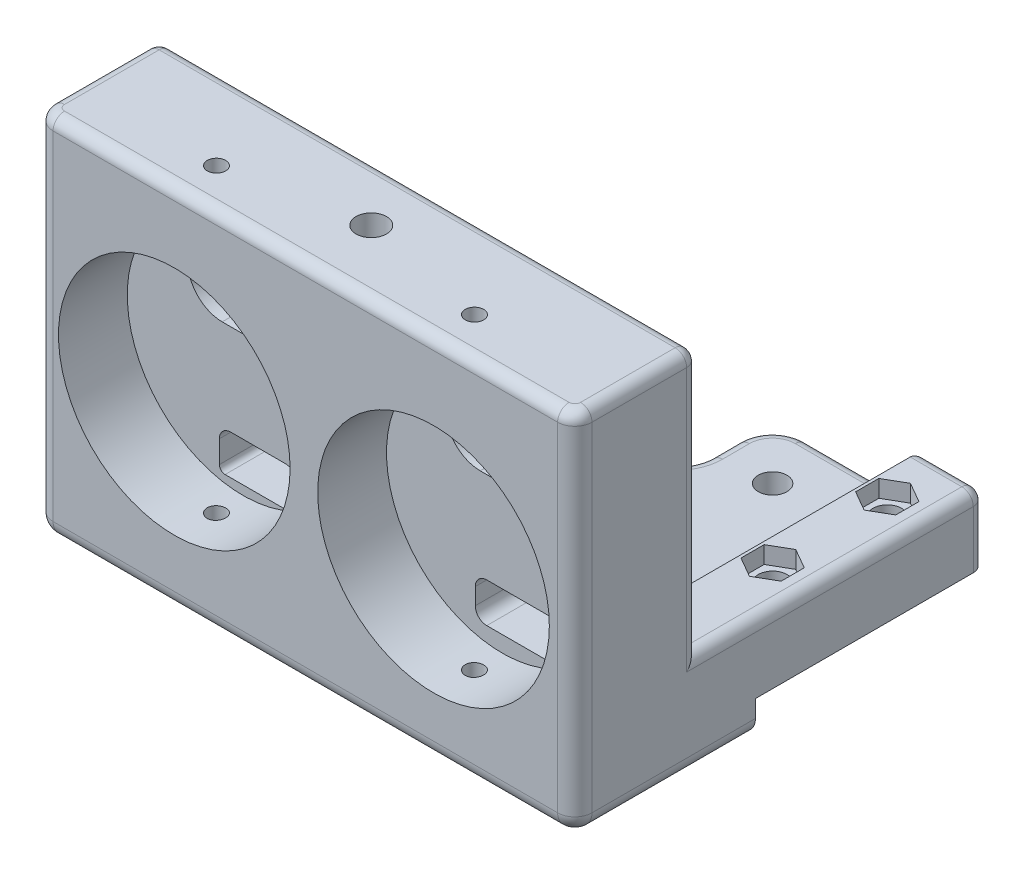
SolidWorks part; units mm, degrees
ref_plane "Ebene vorne" through (0, 0, 0) normal (0, 0, 1) x (1, 0, 0)
ref_plane "Ebene oben" through (0, 0, 0) normal (0, 1, 0) x (1, 0, 0)
ref_plane "Ebene rechts" through (0, 0, 0) normal (1, 0, 0) x (0, 0, -1)
sketch "Skizze1" plane through (0, 0, 0) normal (0, 0, 1) x (1, 0, 0)
  line L1 (174.4691, 28.0437) -> (80.4691, 28.0437)
  line L2 (174.4691, 28.0437) -> (174.4691, -35.9563)
  line L3 (174.4691, -35.9563) -> (80.4691, -35.9563)
  line L4 (80.4691, 28.0437) -> (80.4691, -35.9563)
extrude "Aufsatz-Linear austragen1" add sketch "Skizze1" along normal blind 21.5
sketch "Skizze2" plane through (0, 0, 0) normal (0, 0, -1) x (-1, 0, 0)
  line L5 (-174.4691, -35.9563) -> (-174.4691, 28.0437) construction
  line L6 (-174.4691, -17.9563) -> (-80.4691, -17.9563)
  line L7 (-174.4691, -17.9563) -> (-174.4691, -29.9563)
  line L8 (-174.4691, -29.9563) -> (-80.4691, -29.9563)
  line L9 (-80.4691, -17.9563) -> (-80.4691, -29.9563)
  line L10 (-80.4691, 28.0437) -> (-80.4691, -35.9563) construction
  line L16 (-80.4691, -35.9563) -> (-174.4691, -35.9563) construction
  dimension "D1" = 94
  dimension "D2" = 6
  dimension "D3" = 12
extrude "Aufsatz-Linear austragen2" add sketch "Skizze2" along normal blind 50
fillet "Verrundung1" radius 3 1 edges at (174.4691, -3.9563, 21.5)
sketch "Skizze3" plane through (0, -17.9563, 0) normal (0, 1, 0) x (1, 0, 0)
  line L0 (80.4691, 0) -> (174.4691, 0) construction
  line L1 (91.4691, 0) -> (163.4691, 0)
  line L2 (91.4691, 0) -> (91.4691, 27.1226)
  line L3 (89.4691, 50) -> (163.4691, 50)
  line L4 (163.4691, 0) -> (163.4691, 50)
  line L5 (80.4691, 50) -> (174.4691, 50) construction
  line L6 (80.4691, 50) -> (80.4691, 0) construction
  line L11 (174.4691, 50) -> (174.4691, 0) construction
  line L12 (89.4691, 50) -> (80.4691, 50)
  line L14 (91.4691, 27.1226) -> (80.4691, 27.1226)
  line L15 (80.4691, 50) -> (80.4691, 27.1226)
  dimension "D1" = 11
  dimension "D2" = 50
  dimension "D3" = 11
extrude "Schnitt-Linear austragen1" cut sketch "Skizze3" against normal blind 8
sketch "Skizze6" plane through (0, 0, 0) normal (0, 0, -1) x (-1, 0, 0)
  line L1 (-174.4691, -29.9563) -> (-80.4691, -29.9563)
  line L2 (-174.4691, -29.9563) -> (-174.4691, -35.9563)
  line L3 (-174.4691, -35.9563) -> (-80.4691, -35.9563)
  line L4 (-80.4691, -29.9563) -> (-80.4691, -35.9563)
extrude "Aufsatz-Linear austragen3" add sketch "Skizze6" along direction (0, 0, -1) on the side of the normal blind 10
sketch "Skizze7" plane through (0, 0, 21.5) normal (0, 0, 1) x (1, 0, 0)
  circle A0 centre (104.6099, -4.2584) radius 20.2
  circle A1 centre (149.8248, -5.4669) radius 20.2
extrude "Schnitt-Linear austragen2" cut sketch "Skizze7" against normal blind 12
fillet "Verrundung2" radius 3 1 edges at (80.4691, -3.9563, 21.5)
sketch "Skizze8" plane through (0, 0, 0) normal (0, 0, -1) x (-1, 0, 0)
  line L0 (-91.4691, -25.9563) -> (-163.4691, -25.9563) construction
  line L1 (-113.9691, -15.9563) -> (-100.4691, -15.9563)
  line L2 (-113.9691, -15.9563) -> (-113.9691, -22.8563)
  line L3 (-113.9691, -22.8563) -> (-100.4691, -22.8563)
  line L4 (-100.4691, -15.9563) -> (-100.4691, -22.8563)
  line L5 (-163.4691, -25.9563) -> (-80.4691, -25.9563) construction
  line L6 (-108.9691, 5.9549) -> (-100.9691, 5.9549) construction
  line L7 (-108.9691, 11.9549) -> (-100.9691, 11.9549)
  line L8 (-108.9691, -0.0451) -> (-100.9691, -0.0451)
  line L9 (-153.9691, 5.9549) -> (-145.9691, 5.9549) construction
  line L10 (-153.9691, 11.9549) -> (-145.9691, 11.9549)
  line L11 (-153.9691, -0.0451) -> (-145.9691, -0.0451)
  line L12 (-174.4691, 28.0437) -> (-80.4691, 28.0437) construction
  line L13 (-145.1084, -15.9563) -> (-160.0277, -15.9563)
  line L14 (-145.1084, -15.9563) -> (-145.1084, -22.8563)
  line L15 (-145.1084, -22.8563) -> (-160.0277, -22.8563)
  line L16 (-160.0277, -15.9563) -> (-160.0277, -22.8563)
  arc A0 (-108.9691, 11.9549) -> (-108.9691, -0.0451) centre (-108.9691, 5.9549) ccw
  arc A1 (-100.9691, -0.0451) -> (-100.9691, 11.9549) centre (-100.9691, 5.9549) ccw
  arc A2 (-153.9691, 11.9549) -> (-153.9691, -0.0451) centre (-153.9691, 5.9549) ccw
  arc A3 (-145.9691, -0.0451) -> (-145.9691, 11.9549) centre (-145.9691, 5.9549) ccw
  point P11 (-104.9691, 5.9549)
  point P18 (-149.9691, 5.9549)
  point P29 (-127.4691, 28.0437)
  point P30 (0, 0)
  dimension "D5" = 22.5
  dimension "D1" = 9
  dimension "D2" = 13.5
  dimension "D3" = 3.1
  dimension "D4" = 10
  dimension "D6" = 22.5
extrude "Schnitt-Linear austragen3" cut sketch "Skizze8" against normal blind 20
sketch "Skizze9" plane through (0, -29.9563, 0) normal (0, -1, 0) x (-1, 0, 0)
  line L1 (-174.4691, 10) -> (-80.4691, 10) construction
  line L2 (-80.4691, 50) -> (-80.4691, 10) construction
  line L3 (-167.4691, 20) -> (-147.4691, 20) construction
  circle A0 centre (-167.4691, 20) radius 2.5
  circle A1 centre (-147.4691, 20) radius 2.5
  circle A2 centre (-127.4691, 20) radius 2.5
  circle A3 centre (-107.4691, 20) radius 2.5
  circle A4 centre (-87.4691, 20) radius 2.5
  circle A5 centre (-147.4691, 40) radius 2.5
  circle A6 centre (-127.4691, 40) radius 2.5
  circle A7 centre (-107.4691, 40) radius 2.5
  circle A8 centre (-87.4691, 40) radius 2.5
  circle A9 centre (-147.4691, 60) radius 2.5
  circle A10 centre (-127.4691, 60) radius 2.5
  circle A11 centre (-107.4691, 60) radius 2.5
  circle A12 centre (-87.4691, 60) radius 2.5
  circle A13 centre (-167.4691, 40) radius 2.5
  circle A14 centre (-167.4691, 60) radius 2.5
  point P8 (-127.4691, 10)
  dimension "D6" = 5
  dimension "D1" = 10
  dimension "D2" = 87
  dimension "D5" = 20
  dimension "D3" = 5
  dimension "D4" = 3
extrude "Schnitt-Linear austragen4" cut sketch "Skizze9" against normal blind 20
fillet "Verrundung4" radius 1 1 edges at (100.4691, -22.8563, 4.75)
fillet "Verrundung5" radius 3 5 edges at (80.4691, -35.9563, 4.25) (81.3478, -35.9563, 20.6213) (174.4691, -35.9563, 4.25) (173.5904, -35.9563, 20.6213) (127.4691, -35.9563, 21.5)
sketch "Skizze12" plane through (0, 28.0437, 0) normal (0, 1, 0) x (1, 0, 0)
  circle A0 centre (127.4691, -10) radius 2.65
  circle A1 centre (127.4691, 20) radius 2.5 construction
  dimension "D1" = 0
  dimension "D2" = 30
extrude "Schnitt-Linear austragen6" cut sketch "Skizze12" against normal blind 5.5
fillet "Verrundung8" radius 2 7 edges at (100.4691, -15.9563, 4.75) (113.9691, -15.9563, 4.75) (113.9691, -22.8563, 10) (160.0277, -15.9563, 4.75) (145.1084, -22.8563, 4.75) (145.1084, -15.9563, 4.75) (160.0277, -22.8563, 4.75)
sketch "Skizze24" plane through (0, -17.9563, 0) normal (0, 1, 0) x (1, 0, 0)
  line L1 (87.4691, 15.9585) -> (90.9691, 17.9793)
  line L2 (90.9691, 17.9793) -> (90.9691, 22.0207)
  line L3 (90.9691, 22.0207) -> (87.4691, 24.0415)
  line L4 (87.4691, 24.0415) -> (83.9691, 22.0207)
  line L5 (83.9691, 22.0207) -> (83.9691, 17.9793)
  line L6 (83.9691, 17.9793) -> (87.4691, 15.9585)
  circle A0 centre (87.4691, 20) radius 3.5 construction
  dimension "D1" = 7
extrude "Schnitt-Linear austragen12" cut sketch "Skizze24" against normal blind 3
ref_plane "Ebene1" through (111.9691, -15.9563, 0) normal (1, 0, 0) x (0, 0, -1)
sketch "Skizze27" plane through (0, 28.0437, 0) normal (0, 1, 0) x (1, 0, 0)
  line L0 (171.4691, -21.5) -> (83.4691, -21.5) construction
  circle A0 centre (104.9691, -14.5) radius 1.6
  circle A1 centre (149.9691, -14.5) radius 1.6
  circle A2 centre (127.4691, -10) radius 2.65 construction
  dimension "D1" = 22.5
  dimension "D2" = 45
  dimension "D3" = 7
extrude "Schnitt-Linear austragen15" cut sketch "Skizze27" against normal blind 65
fillet "Verrundung9" radius 2 1 edges at (127.4691, 28.0437, 0)
fillet "Verrundung10" radius 2 17 edges at (168.9691, -17.9563, -50) (80.4691, -17.9563, -13.5613) (174.4691, 27.4579, 0.5858) (174.4691, 28.0437, 10.25) (173.5904, 28.0437, 20.6213) (127.4691, 28.0437, 21.5) (81.3478, 28.0437, 20.6213) (80.4691, 28.0437, 10.25) (80.4691, 27.4579, 0.5858) (174.4691, 4.0437, 0) (80.4691, 4.0437, 0) (80.4691, -21.9563, -27.1226) (91.4691, -21.9563, -27.1226) (85.9691, -17.9563, -27.1226) (174.4691, -17.9563, -25) (163.4691, -21.9563, -50) (174.4691, -23.9563, -50)
sketch "Skizze28" plane through (0, 0, 0) normal (0, 0, -1) x (-1, 0, 0)
  line L1 (-127.4691, 26.0437) -> (-127.4691, -29.9563) construction
  line L2 (-82.4691, 26.0437) -> (-172.4691, 26.0437) construction
  line L3 (-80.4691, -29.9563) -> (-174.4691, -29.9563) construction
sketch "Skizze29" plane through (0, 0, 0) normal (0, 0, -1) x (-1, 0, 0)
  circle A0 centre (-100, 17) radius 1.75
extrude "Schnitt-Linear austragen17" cut sketch "Skizze29" against normal blind 4 contours A0
sketch "Skizze30" plane through (0, -29.9563, 0) normal (0, -1, 0) x (1, 0, 0)
  circle A0 centre (97.4691, -30) radius 1.6
  circle A1 centre (87.4691, -20) radius 2.5 construction
  dimension "D1" = 10
  dimension "D2" = 10
extrude "Schnitt-Linear austragen18" cut sketch "Skizze30" against normal blind 8 contours A0
chamfer "Fase3" distance 4 angle 15 1 edges at (97.4691, -29.9563, -31.6) first distance on face at (97.4691, -25.9563, -28.4)
pattern_linear "Lineares Muster2" count 2 spacing 40 along (1, 0, 0) of "Fase3", "Schnitt-Linear austragen18"
sketch "Skizze31" plane through (0, -25.9563, 0) normal (0, 1, 0) x (1, 0, 0)
  line L0 (97.4691, 51.6034) -> (137.3943, 51.6034)
  line L2 (97.4691, 51.6034) -> (97.4691, 33.2724)
  line L3 (97.4691, 33.2724) -> (137.4691, 33.2724)
  line L4 (137.4691, 33.2724) -> (137.3943, 51.6034)
  dimension "40" = 40
extrude "Schnitt-Linear austragen19" cut sketch "Skizze31" against normal blind 4
fillet "Verrundung22" radius 6 4 edges at (137.4691, -27.9563, -33.2724) (137.4008, -27.9563, -50) (97.4691, -27.9563, -50) (97.4691, -27.9563, -33.2724)
fillet "Verrundung23" radius 2 9 edges at (95.7118, -25.9563, -48.2426) (97.4691, -25.9563, -41.6362) (99.2265, -25.9563, -35.0297) (135.6959, -25.9563, -35.0384) (137.435, -25.9563, -41.6362) (139.1741, -25.9563, -48.234) (117.4568, -25.9563, -33.2724) (154.4472, -25.9563, -50) (85.9691, -25.9563, -50)
fillet "Verrundung24" radius 1 9 edges at (163.4691, -25.9563, -24) (91.4691, -25.9563, -12.5613) (80.4691, -28.9563, -50) (80.4691, -25.9563, -36.5613) (80.4691, -26.5421, -49.4142) (164.0549, -26.5421, -49.4142) (81.0549, -25.9563, -26.5369) (85.9691, -25.9563, -27.1226) (90.8833, -25.9563, -26.5369)
fillet "Verrundung26" radius 2 8 edges at (104.9691, 11.9549, 0) (94.9691, 5.9549, 0) (104.9691, -0.0451, 0) (114.9691, 5.9549, 0) (159.9691, 5.9549, 0) (149.9691, 11.9549, 0) (139.9691, 5.9549, 0) (149.9691, -0.0451, 0)
pattern_linear "Lineares Muster3" count 2 spacing 80 along (1, 0, 0) count 2 spacing 20 along (0, 0, -1) of "Schnitt-Linear austragen12"
equation "\"mm\"=0.7"
